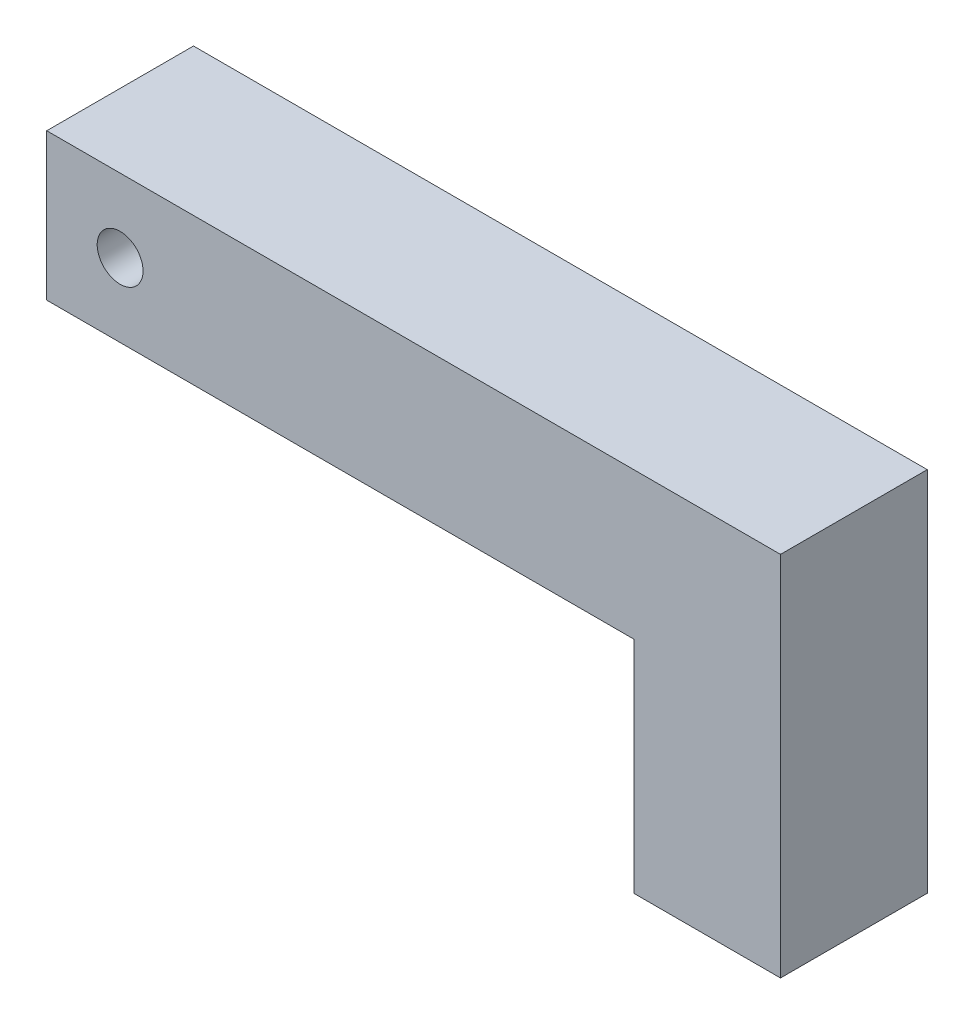
SolidWorks part; units mm, degrees
material "Pine"
ref_plane "Front Plane" through (0, 0, 0) normal (0, 0, 1) x (1, 0, 0)
ref_plane "Top Plane" through (0, 0, 0) normal (0, 1, 0) x (1, 0, 0)
ref_plane "Right Plane" through (0, 0, 0) normal (1, 0, 0) x (0, 0, -1)
sketch "Sketch1" plane through (0, 0, 0) normal (0, 0, 1) x (1, 0, 0)
  line L1 (0, 0) -> (127, 0)
  line L2 (0, 0) -> (0, 25.4)
  line L3 (0, 25.4) -> (127, 25.4)
  line L4 (127, 0) -> (127, 25.4)
  line L5 (127, 0) -> (101.6, 0)
  line L6 (127, 0) -> (127, -38.1)
  line L7 (127, -38.1) -> (101.6, -38.1)
  line L8 (101.6, 0) -> (101.6, -38.1)
  dimension "D1" = 127
  dimension "D2" = 25.4
  dimension "D3" = 38.1
  dimension "D4" = 25.4
extrude "Boss-Extrude1" add sketch "Sketch1" along normal blind 25.4 contours L1 L4 L3 L2 | L1 L8 L7 L6 region at (63.5, 12.7, 0) region at (114.3, -19.05, 0)
sketch "Sketch2" plane through (0, 0, 25.4) normal (0, 0, 1) x (1, 0, 0)
  line L0 (0, 0) -> (0, 25.4) construction
  line L1 (0, 0) -> (101.6, 0) construction
  circle A0 centre (12.7, 12.7) radius 3.9688
  point P6 (0, 0)
  dimension "D1" = 7.9375
  dimension "D2" = 12.7
  dimension "D3" = 12.7
extrude "Cut-Extrude1" cut sketch "Sketch2" against normal through all
